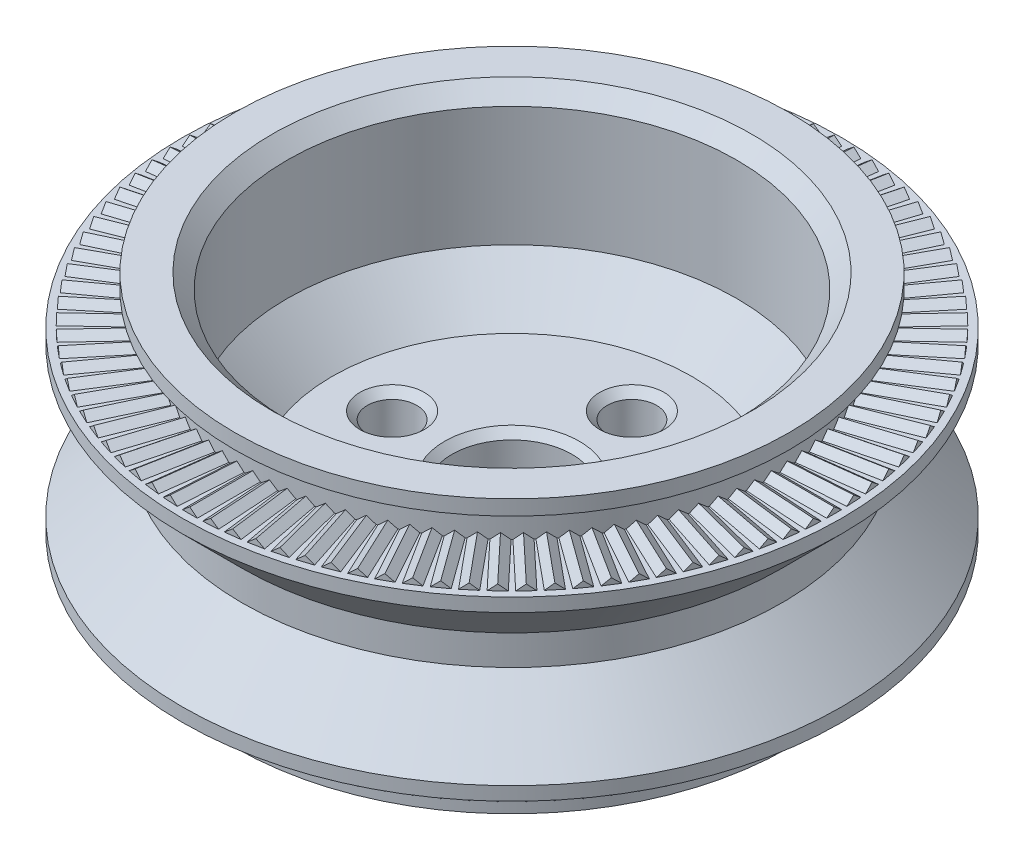
SolidWorks part; units mm, degrees
ref_plane "前视基准面" through (0, 0, 0) normal (0, 0, 1) x (1, 0, 0)
ref_plane "上视基准面" through (0, 0, 0) normal (0, 1, 0) x (1, 0, 0)
ref_plane "右视基准面" through (0, 0, 0) normal (1, 0, 0) x (0, 0, -1)
other "Configuration Table"
sketch "草图1" plane through (0, 0, 0) normal (0, 1, 0) x (1, 0, 0)
  circle A0 centre (0, 0) radius 22
  dimension "D1" = 44
extrude "凸台-拉伸1" add sketch "草图1" along normal mid plane 18.2
sketch "草图2" plane through (0, 0, 0) normal (0, 0, 1) x (1, 0, 0)
  line L0 (22, -9.1) -> (22, 9.1) construction
  line L1 (22, -8.1) -> (17.3, -8.1)
  line L2 (22, -8.1) -> (22, -5.9)
  line L3 (22, -5.9) -> (17.3, -5.9)
  line L4 (17.3, -8.1) -> (17.3, -5.9)
  line L5 (-22, -9.1) -> (22, -9.1) construction
  line L6 (18.5, -9.1) -> (22, -9.1)
  line L7 (18.5, -9.1) -> (18.5, -8.1)
  line L8 (18.5, -8.1) -> (22, -8.1)
  line L9 (22, -9.1) -> (22, -8.1)
  dimension "D1" = 4.7
  dimension "D2" = 18.5
  dimension "D3" = 3.2
  dimension "D4" = 1
ref_axis "基准轴1" through (0, 9.1, 0) along (0, -1, 0)
revolve "切除-旋转1" cut sketch "草图2" angle 360 about axis through (0, 9.1, 0) along (0, -1, 0) region at (20.25, -8.6, 0) region at (19.65, -7, 0)
mirror "镜向1" about plane through (0, 0, 0) normal (0, 1, 0) of "切除-旋转1"
sketch "草图3" plane through (0, -9.1, 0) normal (0, -1, 0) x (1, 0, 0)
  circle A0 centre (0, 0) radius 15
  dimension "D1" = 30
extrude "切除-拉伸1" cut sketch "草图3" against normal blind 3
sketch "草图4" plane through (0, -6.1, 0) normal (0, -1, 0) x (1, 0, 0)
  circle A0 centre (0, 0) radius 4
  dimension "D1" = 8
extrude "切除-拉伸2" cut sketch "草图4" against normal blind 20
sketch "草图5" plane through (0, -6.1, 0) normal (0, -1, 0) x (1, 0, 0)
  circle A0 centre (-8, 0) radius 1.65
  dimension "D2" = 3.3
  dimension "D1" = 8
extrude "切除-拉伸3" cut sketch "草图5" against normal blind 20
pattern_circular "阵列(圆周)1" count 4 over 360 about axis through (0, 9.1, 0) along (0, -1, 0) of "切除-拉伸3"
extrude "切除-拉伸4" cut sketch "草图3<2>" along normal blind 12 from surface starting at face at (0, 9.1, -6.35)
sketch "草图3<2>" plane through (0, -9.1, 0) normal (0, -1, 0) x (1, 0, 0) same geometry as "草图3"
sketch "草图6" plane through (0, 0, 0) normal (0, 0, 1) x (1, 0, 0)
  line L5 (22, -5.9) -> (22, 5.9) construction
  line L6 (18, -5) -> (22, -5)
  line L7 (18, -5) -> (18, 5)
  line L8 (18, 5) -> (22, 5)
  line L9 (22, -5) -> (22, 5)
  line L10 (18, -5) -> (22, 5) construction
  line L11 (18, 5) -> (22, -5) construction
  point P0 (20, 0)
  dimension "D1" = 4
  dimension "D2" = 10
revolve "切除-旋转2" cut sketch "草图6" angle 360 about axis through (0, 9.1, 0) along (0, -1, 0)
chamfer "倒角1" distance 4 angle 45 2 edges at (0, -5, 18) (0, 5, 18)
chamfer "倒角2" distance 3 angle 45 2 edges at (0, -6.1, -15) (0, -2.9, 15)
chamfer "倒角3" distance 1 angle 45 1 edges at (0, 9.1, 15)
chamfer "倒角4" distance 0.5 angle 45 10 edges at (0, -2.9, -6.35) (1.65, -6.1, -8) (-8, -2.9, 1.65) (-8, -6.1, -1.65) (8, -2.9, 1.65) (8, -6.1, 1.65) (0, -2.9, 4) (0, -6.1, -4) (0, -2.9, 9.65) (-1.65, -6.1, 8)
sketch "草图7" plane through (0, 0, 0) normal (0, 0, 1) x (1, 0, 0)
  line L0 (-0.5, 5.9) -> (0, 6.3)
  line L1 (22, 5.9) -> (-22, 5.9) construction
  line L2 (0, 6.3) -> (0.5, 5.9)
  line L3 (0.5, 5.9) -> (-0.5, 5.9)
  dimension "D1" = 1
  dimension "D2" = 0.4
extrude "凸台-拉伸4" add sketch "草图7" along normal blind 5.5 from offset 16
pattern_circular "阵列(圆周)2" count 100 over 360 about axis through (0, 9.1, 0) along (0, -1, 0) of "凸台-拉伸4"
mirror "镜向2" about plane through (0, 0, 0) normal (0, 1, 0) of "阵列(圆周)2"
